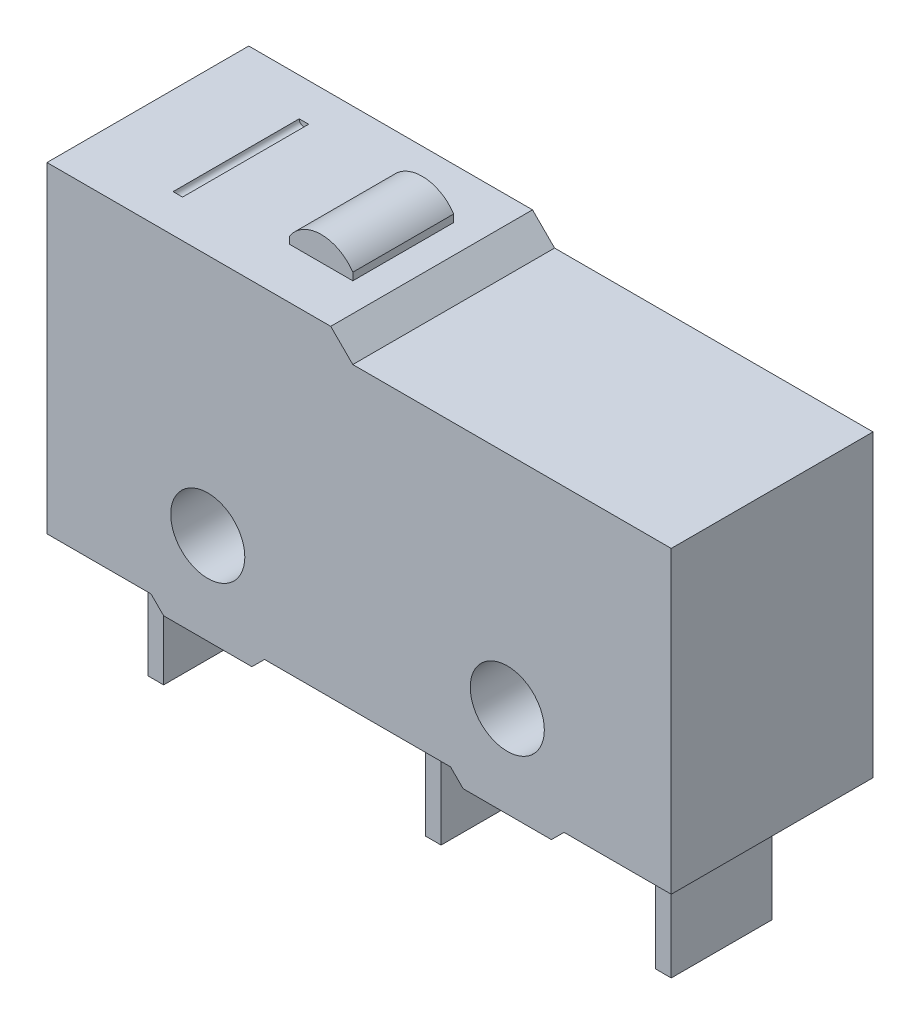
SolidWorks part; units mm, degrees
ref_plane "Płaszczyzna przednia" through (0, 0, 0) normal (0, 0, 1) x (1, 0, 0)
ref_plane "Płaszczyzna górna" through (0, 0, 0) normal (0, 1, 0) x (1, 0, 0)
ref_plane "Płaszczyzna prawa" through (0, 0, 0) normal (1, 0, 0) x (0, 0, -1)
ref_plane "Płaszczyzna1" through (0, 0, 3.2) normal (0, 0, 1) x (1, 0, 0)
sketch "Szkic1" plane through (0, 0, 3.2) normal (0, 0, 1) x (1, 0, 0)
  line L0 (-14.6, -2.9) -> (5.2, -2.9)
  line L1 (5.2, -2.9) -> (5.2, 7.7)
  line L2 (5.2, 7.7) -> (-14.6, 7.7)
  line L3 (-14.6, 7.7) -> (-14.6, -2.9)
extrude "Dodanie-wyciągnięcie1" add sketch "Szkic1" against normal blind 6.4
sketch "Szkic2" plane through (0, 0, -3.2) normal (0, 0, -1) x (-1, 0, 0)
  line L0 (-5.2, 7) -> (5.6, 7)
  line L1 (5.6, 7) -> (5.6, 7.7)
  line L2 (5.6, 7.7) -> (-5.2, 7.7)
  line L3 (-5.2, 7.7) -> (-5.2, 7)
extrude "Wytnij-wyciągnięcie1" cut sketch "Szkic2" against normal through all
sketch "Szkic3" plane through (0, 0, -3.2) normal (0, 0, -1) x (-1, 0, 0)
  line L0 (14.6, -2.5) -> (11.3, -2.5)
  line L1 (11.3, -2.5) -> (11.3, -2.9)
  line L2 (11.3, -2.9) -> (14.6, -2.9)
  line L3 (14.6, -2.9) -> (14.6, -2.5)
extrude "Wytnij-wyciągnięcie2" cut sketch "Szkic3" against normal through all
sketch "Szkic4" plane through (0, 0, -3.2) normal (0, 0, -1) x (-1, 0, 0)
  line L0 (1.8, -2.9) -> (7.7, -2.9)
  line L1 (7.7, -2.9) -> (7.7, -2.5)
  line L2 (7.7, -2.5) -> (1.8, -2.5)
  line L3 (1.8, -2.5) -> (1.8, -2.9)
extrude "Wytnij-wyciągnięcie3" cut sketch "Szkic4" against normal through all
sketch "Szkic5" plane through (0, 0, -3.2) normal (0, 0, -1) x (-1, 0, 0)
  line L0 (-1.8, -2.5) -> (-5.2, -2.5)
  line L1 (-5.2, -2.5) -> (-5.2, -2.9)
  line L2 (-5.2, -2.9) -> (-1.8, -2.9)
  line L3 (-1.8, -2.9) -> (-1.8, -2.5)
extrude "Wytnij-wyciągnięcie4" cut sketch "Szkic5" against normal through all
sketch "Szkic6" plane through (0, 0, -3.2) normal (0, 0, -1) x (-1, 0, 0)
  line L0 (9.0735, -1.175) -> (9.9265, -1.175)
  line L1 (9.9265, 1.175) -> (9.0735, 1.175)
  arc A0 (9.0735, 1.175) -> (9.0735, -1.175) centre (9.5, 0) ccw
  arc A1 (9.9265, -1.175) -> (9.9265, 1.175) centre (9.5, 0) ccw
extrude "Wytnij-wyciągnięcie5" cut sketch "Szkic6" against normal through all
ref_plane "Płaszczyzna2" through (0, 0, 1.6) normal (0, 0, 1) x (1, 0, 0)
sketch "Szkic7" plane through (0, 0, 1.6) normal (0, 0, 1) x (1, 0, 0)
  line L0 (-8.5, 7.9362) -> (-8.5, 7.7)
  line L1 (-8.5, 7.7) -> (-6.5, 7.7)
  line L2 (-6.5, 7.7) -> (-6.5, 7.9362)
  arc A0 (-6.5, 7.9362) -> (-8.5, 7.9362) centre (-7.5, 7.2729) ccw
extrude "Dodanie-wyciągnięcie2" add sketch "Szkic7" against normal blind 3.2
sketch "Szkic8" plane through (0, -2.5, 0) normal (0, -1, 0) x (1, 0, 0)
  line L0 (-4.2, 1.6) -> (-3.7, 1.6)
  line L1 (-3.7, 1.6) -> (-3.7, -1.6)
  line L2 (-3.7, -1.6) -> (-4.2, -1.6)
  line L3 (-4.2, -1.6) -> (-4.2, 1.6)
extrude "Dodanie-wyciągnięcie3" add sketch "Szkic8" along normal blind 3.9
sketch "Szkic9" plane through (0, -2.5, 0) normal (0, -1, 0) x (1, 0, 0)
  line L0 (3.1, 1.6) -> (3.6, 1.6)
  line L1 (3.6, 1.6) -> (3.6, -1.6)
  line L2 (3.6, -1.6) -> (3.1, -1.6)
  line L3 (3.1, -1.6) -> (3.1, 1.6)
extrude "Dodanie-wyciągnięcie4" add sketch "Szkic9" along normal blind 3.9
sketch "Szkic10" plane through (0, -2.5, 0) normal (0, -1, 0) x (1, 0, 0)
  line L0 (-12.5, 1.6) -> (-12.5, -1.6)
  line L1 (-12.5, -1.6) -> (-13, -1.6)
  line L2 (-13, -1.6) -> (-13, 1.6)
  line L3 (-13, 1.6) -> (-12.5, 1.6)
extrude "Dodanie-wyciągnięcie5" add sketch "Szkic10" along normal blind 3.9
draft "Pochylenie1" type of draft neutral plane draft angle 45 faces to draft 1 face at (-5.6, 7.35, 0) neutral plane through (5.2, 7.7, -3.2) neutral plane normal (0, 1, 0) parameters "D1"=45
draft "Pochylenie2" type of draft neutral plane draft angle 45 faces to draft 1 face at (1.8, -2.7, 0) neutral plane through (1.8, -2.5, 3.2) neutral plane normal (0, -1, 0) parameters "D1"=45
draft "Pochylenie3" type of draft neutral plane draft angle 45 faces to draft 1 face at (-11.3, -2.7, 0) neutral plane through (-14.6, -2.5, 3.2) neutral plane normal (0, -1, 0) parameters "D1"=45
draft "Pochylenie4" type of draft neutral plane draft angle 45 faces to draft 2 face at (-7.7, -2.7, 0) face at (-1.8, -2.7, 0) neutral plane through (-7.7, -2.5, 3.2) neutral plane normal (0, -1, 0) parameters "D1"=45
hole_wizard "Otwór Ø2.35 (2.35)1" positions "Szkic12" profile "Szkic11" hole size "Ø2.35" standard "Ansi Metric"
sketch "Szkic12" plane through (0, 0, 3.2) normal (0, 0, 1) x (1, 0, 0)
  point P0 (0, 0)
sketch "Szkic11" plane through (0, 0, 3.2) normal (1, 0, 0) x (0, -1, 0)
  line L0 (0, 0) -> (0, 6.4)
  line L1 (0, 6.4) -> (1.175, 6.4)
  line L2 (1.175, 6.4) -> (1.175, 0)
  line L5 (1.175, 0) -> (0, 0)
  line L11 (0, -6.35) -> (0, 107.95) construction
  dimension "Średnica otworu na wylot" = 2.35
  dimension "Głębokość otworu na wylot" = 6.4
sketch "Szkic13" plane through (0, 7.7, 0) normal (0, 1, 0) x (1, 0, 0)
  line L0 (-14.6, 3.2) -> (-14.6, -3.2) construction
  line L1 (-11.8, 2) -> (-11.5, 2)
  line L2 (-11.8, 2) -> (-11.8, -2)
  line L3 (-11.8, -2) -> (-11.5, -2)
  line L4 (-11.5, 2) -> (-11.5, -2)
  line L5 (-5.6, 3.2) -> (-14.6, 3.2) construction
  dimension "D1" = 2.8
  dimension "D2" = 1.2
  dimension "D3" = 4
  dimension "D4" = 0.3
extrude "Wytnij-wyciągnięcie6" cut sketch "Szkic13" against normal blind 0.15
fillet "Zaokrąglenie1" radius 0.15 1 edges at (-11.5, 7.55, 0)
fillet "Zaokrąglenie2" radius 0.15 1 edges at (-11.8, 7.55, 0)
sketch "Szkic14" plane through (0, 0, 3.2) normal (0, 0, 1) x (1, 0, 0)
  point P0 (0, 0)
  point P1 (-9.5, 0)
sketch "Szkic15" plane through (0, 0, 3.2) normal (0, 0, 1) x (1, 0, 0)
  line L1 (-11.2968, -1.459) -> (-7.7032, -1.459)
  line L2 (-11.2968, -1.459) -> (-11.2968, 1.459)
  line L3 (-11.2968, 1.459) -> (-7.7032, 1.459)
  line L4 (-7.7032, -1.459) -> (-7.7032, 1.459)
  line L5 (-11.2968, -1.459) -> (-7.7032, 1.459) construction
  line L6 (-11.2968, 1.459) -> (-7.7032, -1.459) construction
  point P0 (-9.5, 0)
extrude "Dodanie-wyciągnięcie6" add sketch "Szkic15" against normal through all
sketch "Szkic16" plane through (0, 0, 3.2) normal (0, 0, 1) x (1, 0, 0)
  circle A0 centre (-9.5, 0) radius 1.175
  dimension "D1" = 9.5
extrude "Wytnij-wyciągnięcie7" cut sketch "Szkic16" against normal through all contours A0
